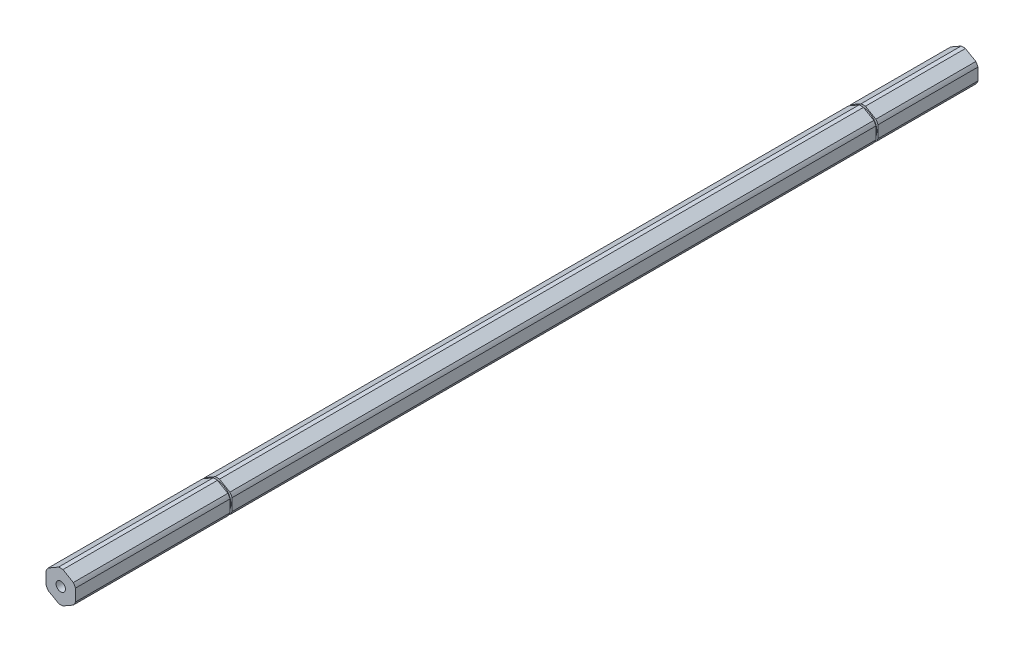
SolidWorks part; units mm, degrees
material "6061-T6 (SS)"
ref_plane "Front Plane" through (0, 0, 0) normal (0, 0, 1) x (1, 0, 0)
ref_plane "Top Plane" through (0, 0, 0) normal (0, 1, 0) x (1, 0, 0)
ref_plane "Right Plane" through (0, 0, 0) normal (1, 0, 0) x (0, 0, -1)
sketch "Sketch1" plane through (0, 0, 0) normal (0, 0, 1) x (1, 0, 0)
  line L1 (0, 7.3323) -> (-6.35, 3.6662)
  line L2 (-6.35, 3.6662) -> (-6.35, -3.6662)
  line L3 (-6.35, -3.6662) -> (0, -7.3323)
  line L4 (0, -7.3323) -> (6.35, -3.6662)
  line L5 (6.35, -3.6662) -> (6.35, 3.6662)
  line L6 (6.35, 3.6662) -> (0, 7.3323)
  circle A0 centre (0, 0) radius 6.35 construction
  circle A1 centre (0, 0) radius 6.858
  dimension "D1" = 12.7
  dimension "D2" = 13.716
extrude "Boss-Extrude1" add sketch "Sketch1" along normal mid plane 388.6403 contours L5 A1 L6 L1 L2 L3 L4 region at (0, 0, 0)
sketch "Sketch2" plane through (0, 0, 194.3202) normal (0, 0, 1) x (1, 0, 0)
  circle A0 centre (0, 0) radius 2.0193
  dimension "D1" = 4.0386
extrude "Cut-Extrude1" [suppressed] cut sketch "Sketch2" against normal through all
sketch "Sketch4" [suppressed] plane through (0, 0, 0) normal (0, 1, 0) x (1, 0, 0)
  line L0 (-2.0193, -194.3202) -> (2.0193, -194.3202) construction
  line L5 (-0.9317, -194.3202) -> (0.9317, -194.3202) construction
  line L7 (9.0297, 151.2672) -> (5.8547, 151.2672)
  line L8 (9.0297, 151.2672) -> (9.0297, 150.3782)
  line L9 (9.0297, 150.3782) -> (5.8547, 150.3782)
  line L10 (5.8547, 151.2672) -> (5.8547, 150.3782)
  line L11 (5.8547, -127.7722) -> (9.0297, -127.7722)
  line L12 (0, 194.3202) -> (0, -194.3202) construction
  line L13 (2.0193, 194.3202) -> (-2.0193, 194.3202) construction
  line L14 (5.8547, -127.7722) -> (5.8547, -126.8832)
  line L15 (5.8547, -126.8832) -> (9.0297, -126.8832)
  line L16 (9.0297, -127.7722) -> (9.0297, -126.8832)
  dimension "D1" = 0.889
  dimension "D2" = 388.6403
  dimension "D3" = 5.8547
  dimension "D4" = 43.053
  dimension "D5" = 3.175
  dimension "D6" = 3.175
  dimension "D7" = 0.889
  dimension "D8" = 66.548
revolve "Cut-Revolve4" [suppressed] cut sketch "Sketch4" angle 360 about L12
hole_wizard "#10-32 Tapped Hole1" positions "3DSketch1" profile "Sketch5" tap size "#10-32" standard "ANSI Inch"
sketch3d "3DSketch1"
  line L0 (0, 0, 194.3202) -> (0, 0, -194.3202) construction
  point P0 (0, 0, 194.3202)
sketch "Sketch5" plane through (0, 0, 194.3202) normal (1, 0, 0) x (0, -1, 0)
  line L0 (0, 0) -> (0, 13.1513)
  line L1 (0, 13.1513) -> (2.0193, 11.938)
  line L2 (2.0193, 11.938) -> (2.0193, 0)
  line L5 (2.0193, 0) -> (0, 0)
  line L10 (0, 13.1513) -> (-2.0193, 11.938) construction
  line L11 (0, -6.35) -> (0, 107.95) construction
  dimension "Tap Drill Dia." = 4.0386
  dimension "Tap Drill Depth" = 11.938
  dimension "Drill Angle" = 118
cosmetic thread "Hole Thread1" parameters "D1"=9.652, "D2"=4.826
sketch "Sketch6" plane through (0, 0, -194.3202) normal (0, 0, -1) x (-1, 0, 0)
  circle A0 centre (0, 0) radius 3.175
  dimension "D1" = 6.35
extrude "Cut-Extrude2" cut sketch "Sketch6" against normal blind 6.35
sketch "Sketch8" plane through (0, 0, 0) normal (0, 1, 0) x (1, 0, 0)
  line L0 (0, 194.3202) -> (0, -194.3202) construction
  line L1 (0.9317, 194.3202) -> (-0.9317, 194.3202) construction
  line L2 (-0.9317, -194.3202) -> (0.9317, -194.3202) construction
  line L4 (5.8547, 151.2672) -> (9.0297, 151.2672)
  line L5 (5.8547, 151.2672) -> (5.8547, 150.3782)
  line L6 (5.8547, 150.3782) -> (9.0297, 150.3782)
  line L7 (9.0297, 151.2672) -> (9.0297, 150.3782)
  line L8 (5.8547, -127.7722) -> (9.0297, -127.7722)
  line L9 (5.8547, -127.7722) -> (5.8547, -126.8832)
  line L10 (5.8547, -126.8832) -> (9.0297, -126.8832)
  line L11 (9.0297, -127.7722) -> (9.0297, -126.8832)
  dimension "D1" = 0.889
  dimension "D2" = 0.889
  dimension "D3" = 3.175
  dimension "D4" = 3.175
  dimension "D5" = 5.8547
  dimension "D6" = 43.053
  dimension "D7" = 66.548
revolve "Cut-Revolve5" cut sketch "Sketch8" angle 360 about L0
equation "\"D1@Boss-Extrude1\"=14.25"
equation "\"D1@Cut-Extrude2\"=0.25in"
